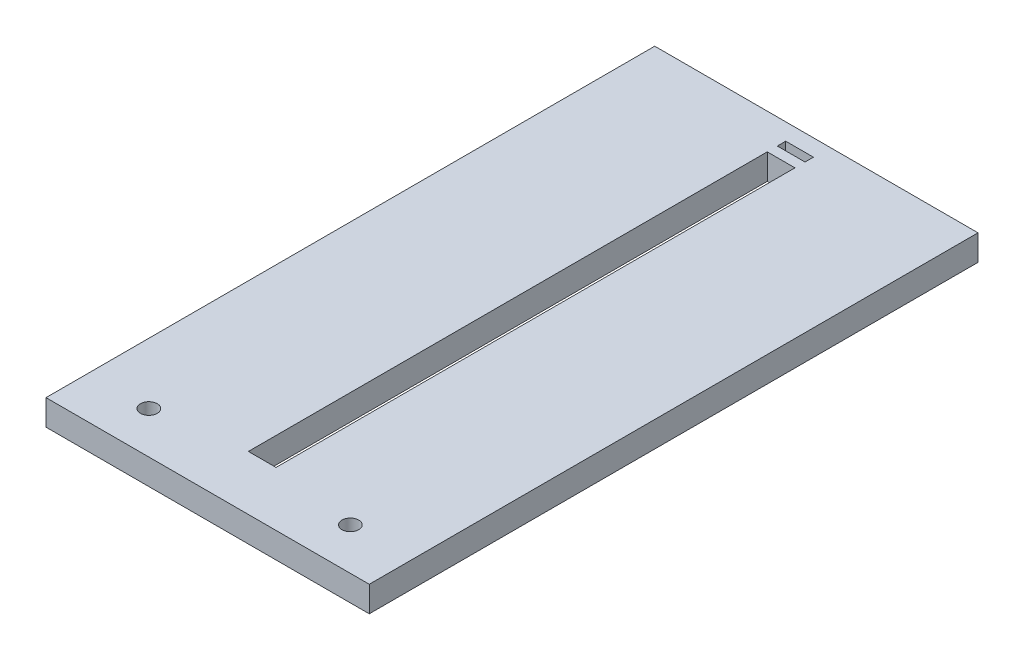
SolidWorks part; units mm, degrees
ref_plane "Front Plane" through (0, 0, 0) normal (0, 0, 1) x (1, 0, 0)
ref_plane "Top Plane" through (0, 0, 0) normal (0, 1, 0) x (1, 0, 0)
ref_plane "Right Plane" through (0, 0, 0) normal (1, 0, 0) x (0, 0, -1)
sketch "Sketch1" plane through (0, 0, 0) normal (0, 1, 0) x (1, 0, 0)
  line L1 (-19.25, 0) -> (19.25, 0)
  line L2 (-19.25, 0) -> (-19.25, 72.5)
  line L3 (-19.25, 72.5) -> (19.25, 72.5)
  line L4 (19.25, 0) -> (19.25, 72.5)
  point P5 (0, 0)
  dimension "D1" = 38.5
  dimension "D2" = 72.5
extrude "Boss-Extrude1" add sketch "Sketch1" along normal blind 3.05 contours L2 | L1 L4 L3 L2 | L4 region at (0, 0, -36.25)
sketch "Sketch4" plane through (0, 3.05, 0) normal (0, 1, 0) x (1, 0, 0)
  line L0 (-19.25, 72.5) -> (19.25, 72.5) construction
  line L2 (-19.25, 0) -> (19.25, 0) construction
  line L3 (1.65, 70.5) -> (-1.65, 70.5)
  line L4 (-1.65, 70.5) -> (-1.65, 69.5)
  line L5 (-1.65, 69.5) -> (1.65, 69.5)
  line L6 (1.65, 69.5) -> (1.65, 70.5)
  line L7 (0, 0) -> (0, 72.5) construction
  line L9 (1.65, 68.3) -> (-1.65, 68.3)
  line L10 (-1.65, 68.3) -> (-1.65, 6.5)
  line L11 (-1.65, 6.5) -> (1.65, 6.5)
  line L12 (1.65, 6.5) -> (1.65, 68.3)
  point P6 (0, 6.5)
  point P10 (0, 70.5)
  point P22 (0, 68.3)
  dimension "D1" = 2
  dimension "D2" = 1
  dimension "D3" = 1.2
  dimension "D4" = 3.3
  dimension "D7" = 6.5
extrude "Cut-Extrude1" cut sketch "Sketch4" against normal through all contours L5 L7 L3 L4 | L11 L7 L9 L10 | L7 L11 L12 L9 | L7 L5 L6 L3 | L6 L3 L4 L5 region at (0.825, 3.05, -70) region at (0.825, 3.05, -37.4) region at (-0.825, 3.05, -37.4) region at (-0.825, 3.05, -70)
sketch "Sketch7" plane through (0, 3.05, 0) normal (0, 1, 0) x (1, 0, 0)
  line L0 (0, 0) -> (-12, 0)
  line L1 (-19.25, 0) -> (19.25, 0) construction
  line L2 (-12, 0) -> (-12, 5)
  line L4 (0, 0) -> (0, 70) construction
  circle A0 centre (-12, 5) radius 1
  circle A2 centre (12, 5) radius 1
  dimension "D3" = 2
  dimension "D1" = 12
  dimension "D2" = 5
extrude "Cut-Extrude4" cut sketch "Sketch7" against normal through all contours A0 L2 | L2 A0 | A2 region at (-11.3129, 3.05, -4.3129)
